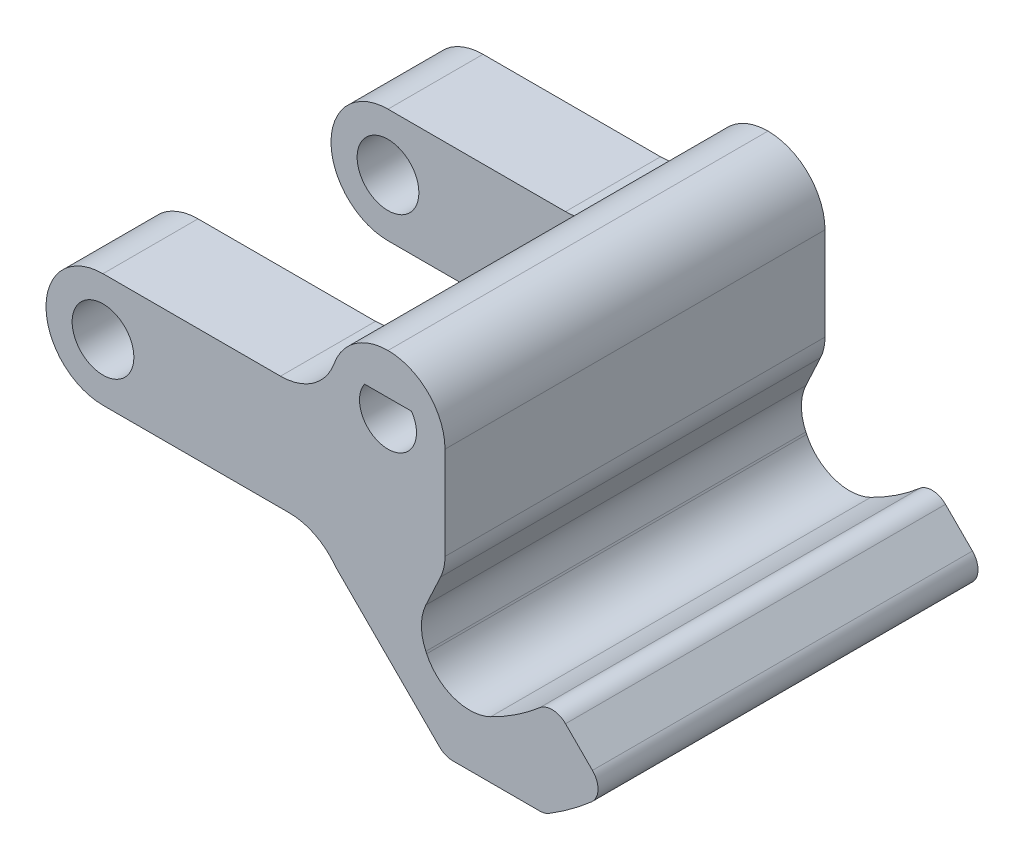
SolidWorks part; units mm, degrees
material "PBT General Purpose"
ref_plane "Front Plane" through (0, 0, 0) normal (0, 0, 1) x (1, 0, 0)
ref_plane "Top Plane" through (0, 0, 0) normal (0, 1, 0) x (1, 0, 0)
ref_plane "Right Plane" through (0, 0, 0) normal (1, 0, 0) x (0, 0, -1)
sketch "Sketch2" plane through (0, 0, 0) normal (0, 0, 1) x (1, 0, 0)
  line L1 (-6, 6) -> (6, 6)
  line L2 (-6, 6) -> (-6, -16)
  line L4 (6, 6) -> (6, -10.8869)
  line L5 (17.3241, -17.3241) -> (22.981, -22.981)
  line L6 (0, 0) -> (17.3241, -17.3241) construction
  line L7 (0, -24.5) -> (0, 0) construction
  line L10 (-6, -16) -> (6, -28)
  line L11 (6, -10.8869) -> (3, -17.3204)
  line L12 (3, -17.3204) -> (6, -23.7539)
  line L13 (6, -28) -> (16.5, -28)
  arc A0 (6, -23.7539) -> (17.3241, -17.3241) centre (0, 0) ccw
  arc A1 (16.5, -28) -> (22.981, -22.981) centre (0, 0) ccw
  circle A2 centre (0, 0) radius 3
  arc A3 (0, -24.5) -> (6, -23.7539) centre (0, 0) ccw construction
  dimension "D2" = 6
  dimension "D5" = 24.5
  dimension "D3" = 12
  dimension "D4" = 45
  dimension "D6" = 8
  dimension "D8" = 45
  dimension "D9" = 25
  dimension "D10" = 25
  dimension "D11" = 3
  dimension "D7" = 28
extrude "Boss-Extrude1" add sketch "Sketch2" along normal mid plane 40
fillet "Fillet1" radius 6 2 edges at (6, 6, 0) (-6, 6, 0)
fillet "Fillet2" radius 2 5 edges at (22.981, -22.981, 0) (17.3241, -17.3241, 0) (-6, -16, 0) (16.5, -28, 0) (6, -28, 0)
fillet "Fillet4" radius 5 3 edges at (6, -10.8869, 0) (3, -17.3204, 0) (6, -23.7539, 0)
sketch "Sketch3" plane through (0, 0, 20) normal (0, 0, 1) x (1, 0, 0)
  line L0 (-6, -2) -> (-36, -2)
  line L1 (-6, 0) -> (-6, -15.1716) construction
  line L2 (-36, -2) -> (-36, -14)
  line L3 (-36, -14) -> (-6, -14)
  line L4 (-6, -14) -> (-6, -2)
  line L5 (-30, -8) -> (-36, -8) construction
  circle A0 centre (-30, -8) radius 3.25
  dimension "D2" = 6
  dimension "D1" = 6.5
  dimension "D3" = 8
  dimension "D4" = 12
  dimension "D5" = 30
extrude "Boss-Extrude2" add sketch "Sketch3" against normal blind 10
fillet "Fillet3" radius 6 4 edges at (-36, -14, 15) (-36, -2, 15) (-6, -14, 15) (-6, -2, 15)
mirror "Mirror1" about plane through (0, 0, 0) normal (0, 0, 1) of "Fillet3", "Boss-Extrude2"
sketch "Sketch4" plane through (0, 0, -20) normal (0, 0, -1) x (-1, 0, 0)
  line L0 (-2.4718, 1.7) -> (2.4718, 1.7)
  circle A0 centre (0, 0) radius 3 construction
  arc A1 (2.4718, 1.7) -> (-2.4718, 1.7) centre (0, 0) ccw
  dimension "D1" = 1.7
extrude "Boss-Extrude3" add sketch "Sketch4" against normal up to surface (40 mm away) up to face at (1.1571, -14.8675, 20)
equation "\"D4@Sketch2\"=70-25"
equation "\"D2@Sketch3\"=\"D4@Sketch3\"/2"
